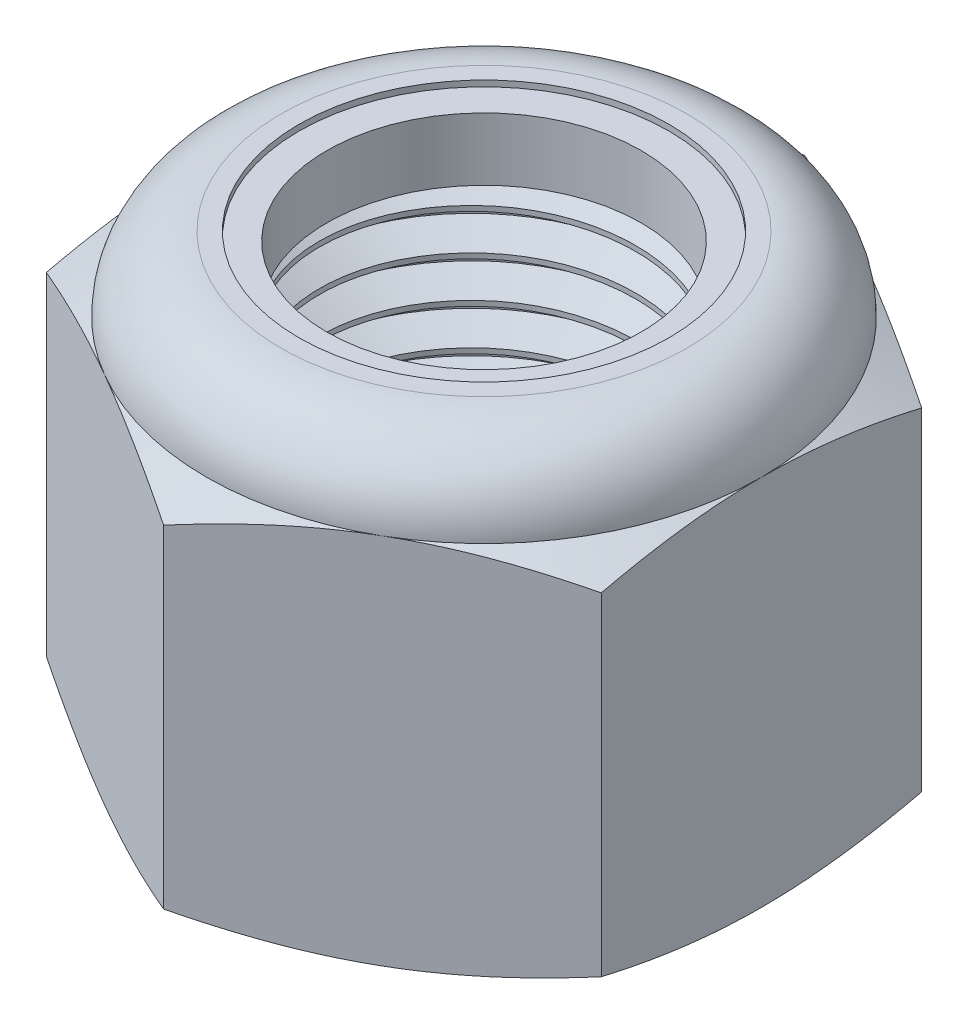
SolidWorks part; units mm, degrees
ref_plane "Front" through (0, 0, 0) normal (0, 0, 1) x (1, 0, 0)
ref_plane "Top" through (0, 0, 0) normal (0, 1, 0) x (1, 0, 0)
ref_plane "Right" through (0, 0, 0) normal (1, 0, 0) x (0, 0, -1)
sketch "Sketch1" plane through (0, 0, 0) normal (1, 0, 0) x (0, 0, -1)
  line L0 (0, 0) -> (0, 11.5094) construction
  line L1 (7.1437, 0) -> (-7.1437, 0) construction
  line L2 (-4.7625, 11.5094) -> (4.7625, 11.5094) construction
  line L3 (4.7625, 11.5094) -> (4.7625, 10.451) construction
  point P9 (-4.7625, 11.5094)
  point P10 (4.7625, 11.5094)
  point P11 (7.1437, 0)
  dimension "Height" = 11.5094
  dimension "Hex Flats" = 14.2875
  dimension "Thread Dia" = 9.525
  dimension "Thread Pitch" = 1.0583
sketch "Sketch13" plane through (0, 0, 0) normal (0, 1, 0) x (1, 0, 0)
  line L1 (0, 8.2489) -> (-7.1438, 4.1244)
  line L2 (-7.1438, 4.1244) -> (-7.1437, -4.1244)
  line L3 (-7.1437, -4.1244) -> (0, -8.2489)
  line L4 (0, -8.2489) -> (7.1438, -4.1244)
  line L5 (7.1438, -4.1244) -> (7.1438, 4.1244)
  line L6 (7.1438, 4.1244) -> (0, 8.2489)
  circle A0 centre (0, 0) radius 7.1437 construction
  circle A1 centre (0, 0) radius 4.7625
  point P11 (0, -4.7625)
  point P13 (0, 4.7625)
extrude "Extrude1" add sketch "Sketch13" along normal up to vertex (11.5094 mm away) up to point (0, 11.5094, 0)
sketch "Sketch5" plane through (0, 0, 0) normal (1, 0, 0) x (0, 0, -1)
  line L0 (0, 0) -> (7.1437, 0)
  line L1 (7.1437, 0) -> (8.2489, 0.5153)
  line L2 (8.2489, 0.5153) -> (8.2489, 9.0758)
  line L3 (8.2489, 9.0758) -> (7.1437, 9.5911)
  line L4 (5.2255, 11.5094) -> (5.2255, 12.7794)
  line L5 (5.2255, 12.7794) -> (9.5189, 12.7794)
  line L6 (9.5189, 12.7794) -> (9.5189, -1.27)
  line L7 (9.5189, -1.27) -> (0, -1.27)
  line L8 (0, -1.27) -> (0, 0)
  line L9 (7.1437, 9.5911) -> (7.1437, 0) construction
  line L12 (8.2489, 11.5094) -> (8.2489, 0) construction
  line L13 (8.2489, 5.7547) -> (9.5189, 5.7547) construction
  line L15 (0, 0) -> (0, 12.7794) construction
  line L18 (7.1437, 0) -> (-7.1437, 0) construction
  line L19 (4.1244, 11.5094) -> (8.2489, 11.5094) construction
  line L20 (0, 12.7794) -> (5.2255, 12.7794) construction
  line L21 (4.1244, 0) -> (8.2489, 0) construction
  arc A0 (7.1437, 9.5911) -> (5.2255, 11.5094) centre (5.2255, 9.5911) ccw
  dimension "D1" = 25
  dimension "D2" = 1.27
  dimension "D4" = 1.9182
revolve "Cut-Revolve3" cut sketch "Sketch5" angle 360 about L15
sketch "Sketch4" plane through (0, 0, 0) normal (1, 0, 0) x (0, 0, -1)
  line L0 (0, 9.5911) -> (5.2388, 9.5911)
  line L1 (5.2388, 9.5911) -> (0, 7.1483)
  line L3 (0, 2.4429) -> (5.2388, 0)
  line L4 (5.2388, 0) -> (0, 0)
  line L5 (0, 0) -> (0, 9.5911) construction
  line L10 (0, 0) -> (0, 11.5094) construction
  line L11 (0, 2.4429) -> (0, 0)
  line L12 (0, 9.5911) -> (0, 7.1483)
  line L13 (6.1867, 9.5911) -> (0, 9.5911) construction
  dimension "D1" = 25
  dimension "D2" = 10.4775
sketch "Sketch6" plane through (0, 0, 0) normal (1, 0, 0) x (0, 0, -1)
  line L0 (0, 9.5911) -> (6.9914, 9.5911)
  line L1 (5.2255, 11.357) -> (2.6128, 11.357)
  line L2 (0, 12.7794) -> (0, 9.5911)
  line L3 (2.6128, 12.7794) -> (0, 12.7794)
  line L4 (0, 12.7794) -> (5.2255, 12.7794) construction
  line L5 (0, 0) -> (0, 12.7794) construction
  line L6 (0, 12.7794) -> (0, 0) construction
  line L7 (2.6128, 11.357) -> (2.6128, 12.7794)
  line L8 (5.2255, 11.5094) -> (5.2255, 11.357) construction
  line L9 (2.6128, 11.357) -> (0, 11.357) construction
  line L10 (0, 11.357) -> (0, 7.1483) construction
  arc A0 (6.9914, 9.5911) -> (5.2255, 11.357) centre (5.2255, 9.5911) ccw
  arc A1 (7.1437, 9.5911) -> (5.2255, 11.5094) centre (5.2255, 9.5911) ccw construction
  dimension "D1" = 0.1524
revolve "Cut-Revolve4" cut sketch "Sketch6" angle 360 about L6
revolve "Cut-Revolve2" cut sketch "Sketch4" angle 360 about L5
sketch "Sketch7" plane through (0, 0, 0) normal (1, 0, 0) x (0, 0, -1)
  line L0 (4.0481, 9.6673) -> (6.9134, 9.6673)
  line L1 (5.2255, 11.2808) -> (4.0481, 11.2808)
  line L2 (4.0481, 11.2808) -> (4.0481, 9.6673)
  line L3 (4.0481, 9.6673) -> (0, 9.6673) construction
  line L4 (0, 9.6673) -> (0, 11.2808) construction
  line L5 (0, 11.2808) -> (4.0481, 11.2808) construction
  line L6 (4.0481, 9.6673) -> (4.0481, 9.5911) construction
  line L7 (0, 9.5911) -> (6.9914, 9.5911) construction
  line L8 (5.2255, 11.2808) -> (5.2255, 11.357) construction
  arc A0 (6.9134, 9.6673) -> (5.2255, 11.2808) centre (5.2255, 9.5911) ccw
  arc A2 (6.9914, 9.5911) -> (5.2255, 11.357) centre (5.2255, 9.5911) ccw construction
  point P15 (4.0481, 11.2808)
  point P18 (-4.6368, 11.2808)
  point P19 (4.6368, 11.2808)
  dimension "D1" = 0.0762
  dimension "D2" = 8.0962
revolve "Revolve2" add sketch "Sketch7" angle 360 about L4
sketch "Sketch2" plane through (0, 0, 0) normal (1, 0, 0) x (0, 0, -1)
  line L0 (-4.7625, 0) -> (-4.7625, 9.5911) construction
  line L1 (0, 0) -> (4.7625, 0)
  line L2 (0, 0) -> (0, 9.5911)
  line L3 (0, 9.5911) -> (4.7625, 9.5911)
  line L4 (4.7625, 0) -> (4.7625, 9.5911)
  line L6 (6.1867, 9.5911) -> (7.1437, 9.5911) construction
  line L7 (0, -4.7625) -> (0, 0) construction
revolve "Revolve1" add sketch "Sketch2" angle 360 about L7
sketch "Sketch9" plane through (0, 0, 0) normal (1, 0, 0) x (0, 0, -1)
  line L0 (4.8771, 10.5833) -> (4.8771, 9.525) construction
  line L1 (4.8771, 9.525) -> (3.9605, 10.0542) construction
  line L2 (3.9605, 10.0542) -> (4.8771, 10.5833) construction
  line L3 (4.0751, 10.1203) -> (4.0751, 9.988) construction
  line L4 (4.7625, 10.5172) -> (4.7625, 9.5911) construction
  line L5 (3.9605, 10.0542) -> (4.0751, 10.0542) construction
  line L6 (4.7625, 10.0542) -> (4.8771, 10.0542) construction
  line L7 (4.8198, 10.0542) -> (4.8198, 10.5503) construction
  line L8 (4.8771, 9.525) -> (4.8198, 10.5503)
  line L9 (4.8198, 10.5503) -> (4.0751, 10.1203)
  line L10 (4.0751, 10.1203) -> (4.0751, 9.988)
  line L11 (4.0751, 9.988) -> (4.8771, 9.525)
  dimension "D1" = 1.0583
  dimension "D2" = 0.1323
sketch "Sketch10" plane through (0, 9.5911, 0) normal (0, 1, 0) x (1, 0, 0)
  circle A1 centre (0, 0) radius 4.7625
  circle A2 centre (0, 0) radius 4.7625
  dimension "D1" = 0
curve "Helix/Spiral1" pitch 1.0583 height 12.5677 turns 11.875
sweep "Cut-Sweep1" cut profiles "Sketch9" path "Helix/Spiral1" align with end faces yes
sketch "Sketch11" plane through (0, 0, 0) normal (1, 0, 0) x (0, 0, -1)
  line L0 (0, 0) -> (0, 11.5094) construction
  line L1 (7.1437, 0) -> (-7.1437, 0) construction
  line L4 (0, 11.5094) -> (0, 0) construction
  line L5 (0, 5.7547) -> (4.7625, 5.7547) construction
  line L6 (0, 0) -> (5.2388, 0)
  line L7 (0, 2.4429) -> (0, 0)
  line L8 (5.2388, 0) -> (0, 2.4429)
  dimension "D1" = 10.4775
  dimension "D2" = 25
revolve "Revolve3" add sketch "Sketch11" angle 360 about L4
sketch "Sketch12" plane through (0, 0, 0) normal (1, 0, 0) x (0, 0, -1)
  line L0 (5.2388, 9.5911) -> (0, 9.5911)
  line L1 (0, 9.5911) -> (0, 0)
  line L2 (0, 0) -> (5.2388, 0)
  line L3 (7.1437, 0) -> (-7.1437, 0) construction
  line L4 (5.2388, 0) -> (5.2388, 9.5911)
  line L5 (-5.2388, 0) -> (5.2388, 0) construction
revolve "Revolve4" add sketch "Sketch12" angle 360 about L0
combine bodies "Combine1" operation type subtract main body 136 bodies to subtract 133
equation "\"D4@Sketch5\" = \"Height@Sketch1\" / 6"
equation "\"D1@Sketch9\" = \"Thread Pitch@Sketch1\""
equation "\"D2@Sketch9\" = \"Thread Pitch@Sketch1\" / 8"
equation "\"D4@Helix/Spiral1\" = \"Thread Pitch@Sketch1\""
equation "\"D3@Helix/Spiral1\" = \"Thread Pitch@Sketch1\" + \"Height@Sketch1\""
equation "\"D2@Sketch4\" = \"Thread Dia@Sketch1\" * 1.1"
equation "\"D1@Sketch11\" = \"Thread Dia@Sketch1\" * 1.1"
equation "\"D2@Sketch7\" = \"Thread Dia@Sketch1\" * .85"
